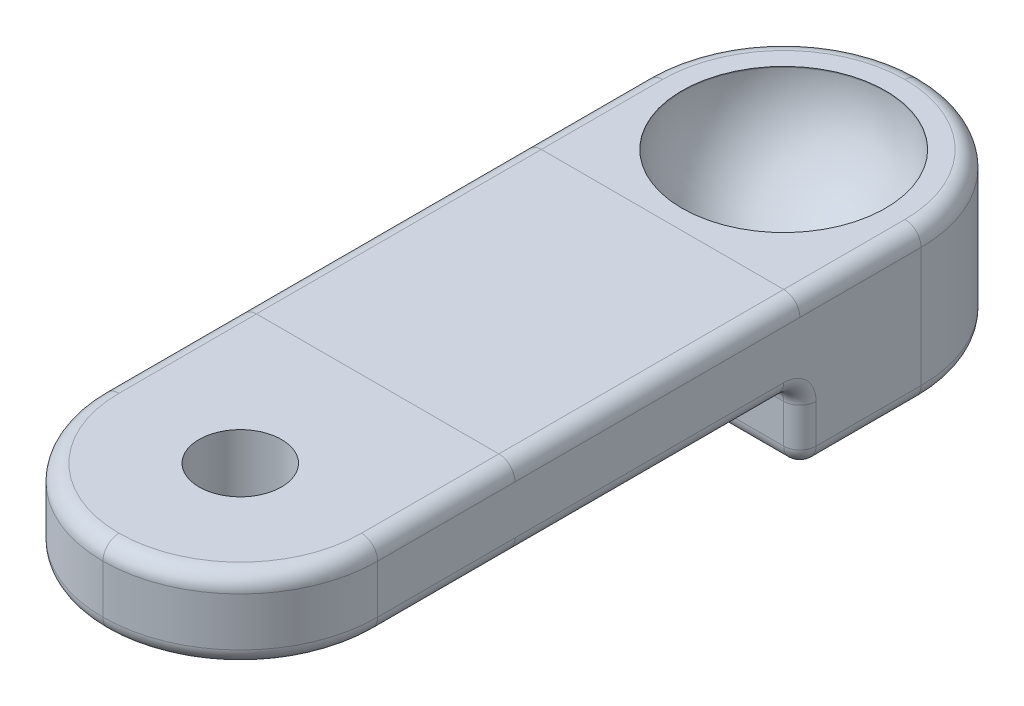
SolidWorks part; units mm, degrees
ref_plane "Front Plane" through (0, 0, 0) normal (0, 0, 1) x (1, 0, 0)
ref_plane "Top Plane" through (0, 0, 0) normal (0, 1, 0) x (1, 0, 0)
ref_plane "Right Plane" through (0, 0, 0) normal (1, 0, 0) x (0, 0, -1)
sketch "ProfileSketch1" plane through (0, 0, 0) normal (1, 0, 0) x (0, 0, -1)
  line L0 (0, 0) -> (34, 0)
  line L1 (34, 0) -> (69.2531, 0)
  line L2 (69.2531, 0) -> (101.2531, 0)
  line L3 (17, 0) -> (17, 2.8642) construction
  line L4 (85.2531, 0) -> (85.2531, 2.8642) construction
  dimension "D1" = 34
  dimension "D2" = 0
  dimension "D4" = 32
  dimension "D3" = 68.2531
extrude "ProfileExtrude-Thin1" add sketch "ProfileSketch1" along normal blind 34 thin thin type one direction wall 10
sketch "DomePadExtensionSketch1" plane through (0, -10, 0) normal (0, -1, 0) x (1, 0, 0)
  line L1 (0, -69.2531) -> (34, -69.2531)
  line L2 (0, -69.2531) -> (0, -101.2531)
  line L3 (0, -101.2531) -> (34, -101.2531)
  line L4 (34, -69.2531) -> (34, -101.2531)
extrude "DomePadExtensionBoss-Extrude1" add sketch "DomePadExtensionSketch1" along normal blind 8.8
fillet "Fillet1" radius 17 1 edges at (34, -5, 0)
fillet "Fillet2" radius 17 1 edges at (0, -5, 0)
sketch "FlangeNutHoleSketch4" plane through (0, 0, 0) normal (0, 1, 0) x (1, 0, 0)
  line L0 (0, 17) -> (0, 34) construction
  line L1 (34, 34) -> (0, 34) construction
  circle A0 centre (17, 17) radius 5.1
  dimension "D1" = 17
  dimension "D3" = 10.2
  dimension "D2" = 17
extrude "FlangeNutHoleCut-Extrude5" cut sketch "FlangeNutHoleSketch4" against normal through all
sketch "DomeIndentSketch6" plane through (0, 0, 0) normal (0, 1, 0) x (1, 0, 0)
  line L4 (0, 69.2531) -> (0, 101.2531) construction
  line L5 (34, 101.2531) -> (0, 101.2531) construction
  circle A0 centre (17, 84.2531) radius 12.6
  dimension "D2" = 17
  dimension "D1" = 25.2
  dimension "D3" = 17
extrude "DomeIndentCut-Extrude8" cut sketch "DomeIndentSketch6" against normal blind 0.1
dome "Dome2" faces to dome 1 distance 12.5 reverse direction yes elliptical dome no face at (17, -0.1, -71.6531) parameters "D1"=12.5
fillet "Fillet3" radius 17 1 edges at (34, -9.4, -101.2531)
fillet "Fillet4" radius 17 1 edges at (0, -9.4, -101.2531)
sketch "FlangeNutHolesSketch2" plane through (0, -10, 0) normal (0, -1, 0) x (1, 0, 0)
  line L0 (32, -31.2943) -> (32, -17) construction
  line L1 (34, -34) -> (0, -34) construction
  circle A0 centre (11.3431, -11.3431) radius 2
  circle A1 centre (22.6569, -11.3431) radius 2
  circle A2 centre (22.6569, -22.6569) radius 2
  circle A3 centre (11.3431, -22.6569) radius 2
  point P16 (17, -17)
  dimension "D2" = 4
  dimension "D1" = 8
  dimension "D4" = 8
  dimension "D3" = 4
fillet "BottomBoundaryFillet5" radius 2 14 edges at (0, -10, -51.6266) (34, -10, -51.6266) (34, -10, -25.5) (29.0208, -10, -4.9792) (4.9792, -10, -4.9792) (0, -10, -25.5) (34, -18.8, -76.7531) (29.0208, -18.8, -96.2739) (4.9792, -18.8, -96.2739) (34, -14.4, -69.2531) (17, -18.8, -69.2531) (0, -14.4, -69.2531) (17, -10, -69.2531) (0, -18.8, -76.7531)
extrude "FlangeNutHolesCut-Extrude1" cut sketch "FlangeNutHolesSketch2" against normal blind 4
fillet "Fillet6" radius 2 10 edges at (34, 0, -51.6266) (34, 0, -25.5) (29.0208, 0, -4.9792) (4.9792, 0, -4.9792) (0, 0, -25.5) (0, 0, -51.6266) (0, 0, -76.7531) (4.9792, 0, -96.2739) (34, 0, -76.7531) (29.0208, 0, -96.2739)
equation "\"D1@ProfileSketch1\"=\"BedSupportLeadScrewPadSize\""
equation "\"StandardWallThickness\"= 3mm"
equation "\"BedToBuildPlateStandoffPadSize\"= 10mm"
equation "\"BuildPlateStandoffHolesDistanceFromLeftOrRight\"= 7mm"
equation "\"BuildPlateStandoffHolesDistanceFromFrontOrBack\"= 41mm"
equation "\"DistanceFromBuildPlateSideToStepperHole\"= ( \"DistanceBetweenLeftToRightStepperHoles\" - \"BuildPlateWidth\" ) / 2'Equals 55.825"
equation "\"DistanceBetweenLeftToRightStepperHoles\"= \"FrontBackRailLength\" - \"StepperMountingHoleOffsetFromLeftOrRightSide\" * 2 - \"StepperMountingHoleDistance\"'Equals 461.65"
equation "\"FrontBackRailLength\"= 510mm"
equation "\"StepperMountingHoleOffsetFromLeftOrRightSide\"= \"StepperMountingHoleOffsetFromItsSide\" + \"RailThickness\""
equation "\"StepperMountingHoleDistance\"= 31mm'Spec"
equation "\"StepperMountingHoleOffsetFromItsSide\"= 5.5mm'Spec"
equation "\"RailThickness\"= .125in'Spec"
equation "\"LeadScrewNutPadSize\"= \"LeadScrewNutMountingHoleFlangeDiameter\" + 2mm'Equals 24"
equation "\"LeadScrewNutInnerShaftFlangeDiameter\"= 10.2mm'Spec"
equation "\"LeadScrewNutMountHoleDiameter\"= \"M3HeatInsertHoleDiameter\""
equation "\"LeadScrewNutMountingHoleFlangeDiameter\"= 22mm'Spec"
equation "\"LeadScrewNutMountingHoleDistance\"= 16mm'Spec"
equation "\"M3HeatInsertHoleDiameter\"= 4mm'Spec"
equation "\"D1@Fillet1\"=\"BedSupportLeadScrewPadSize\"/2"
equation "\"D1@Fillet2\"=\"BedSupportLeadScrewPadSize\"/2"
equation "\"D1@FlangeNutHoleSketch4\"=\"BedSupportLeadScrewPadSize\"  / 2"
equation "\"D2@FlangeNutHoleSketch4\"=\"BedSupportLeadScrewPadSize\" / 2"
equation "\"D3@FlangeNutHoleSketch4\" = \"LeadScrewNutInnerShaftFlangeDiameter\""
equation "\"D2@DomeIndentSketch6\" = \"BedSupportLeadScrewPadSize\" / 2"
equation "\"D3@DomeIndentSketch6\" = \"BedSupportLeadScrewPadSize\" / 2"
equation "\"BedSpringHoleSize\"= 3mm"
equation "\"BuildPlateWidth\"= 350mm'Spec"
equation "\"BuildPlateLength\"= 350mm'Spec"
equation "\"BuildPlateBoreDiameter\"= 5mm'Spec"
equation "\"BuildPlateBoreDepth\"= 3mm'Spec"
equation "\"BuildPlateDepth\"= 8mm'Spec"
equation "\"BuildPlateFlankingHoles\"= 38mm"
equation "\"BuildPlateStandoffHolesDistanceFromFront\"= 7mm"
equation "\"BedSupportLeadScrewPadSize\"= \"LeadScrewNutPadSize\" + 10mm"
equation "\"D1@ProfileExtrude-Thin1\"=\"BedSupportLeadScrewPadSize\""
equation "\"BuildPlateBallDiameter\"= 12mm"
equation "\"BedSupportBuildPlatePadSize\"= \"BuildPlateBallDiameter\" + 20mm"
equation "\"D4@ProfileSketch1\"=\"BedSupportBuildPlatePadSize\""
equation "\"D3@ProfileSketch1\"= \"HypotonusOfStepperAndBuildPlateHoles\" + 1mm'Odd, both physical and CAD required 1mm extra"
equation "\"D1@Fillet3\"=\"BedSupportLeadScrewPadSize\"/2"
equation "\"D1@Fillet4\"=\"BedSupportLeadScrewPadSize\"/2"
equation "\"HypotonusOfStepperAndBuildPlateHoles\"= sqr ( ( \"DistanceFromBuildPlateSideToStepperHole\" + \"BuildPlateStandoffHolesDistanceFromLeftOrRight\" ) ^ 2 + ( \"BuildPlateStandoffHolesDistanceFromFrontOrBack\" - \"BedSupportLeadScrewPadSize\" / 2 ) ^ 2 )"
equation "\"D1@FlangeNutHolesCut-Extrude1\" = \"M3HeatInsertHoleDiameter\""
equation "\"D1@FlangeNutHolesSketch2\"=\"LeadScrewNutMountingHoleDistance\"/2"
equation "\"D2@FlangeNutHolesSketch2\"=\"M3HeatInsertHoleDiameter\""
equation "\"D4@FlangeNutHolesSketch2\"=\"LeadScrewNutMountingHoleDistance\"/2"
equation "\"BallNutDiameter\"= \"BallJointDiameter\" + .2mm'Added .2mm for filament expansion"
equation "\"D1@DomeIndentSketch6\"=\"BallNutDiameter\""
equation "\"D1@DomePadExtensionBoss-Extrude1\" = \"BedSupportBuildPlatePadSize\" - \"BallNutDiameter\" + 2mm"
equation "\"BallJointDiameter\"= 25mm"
